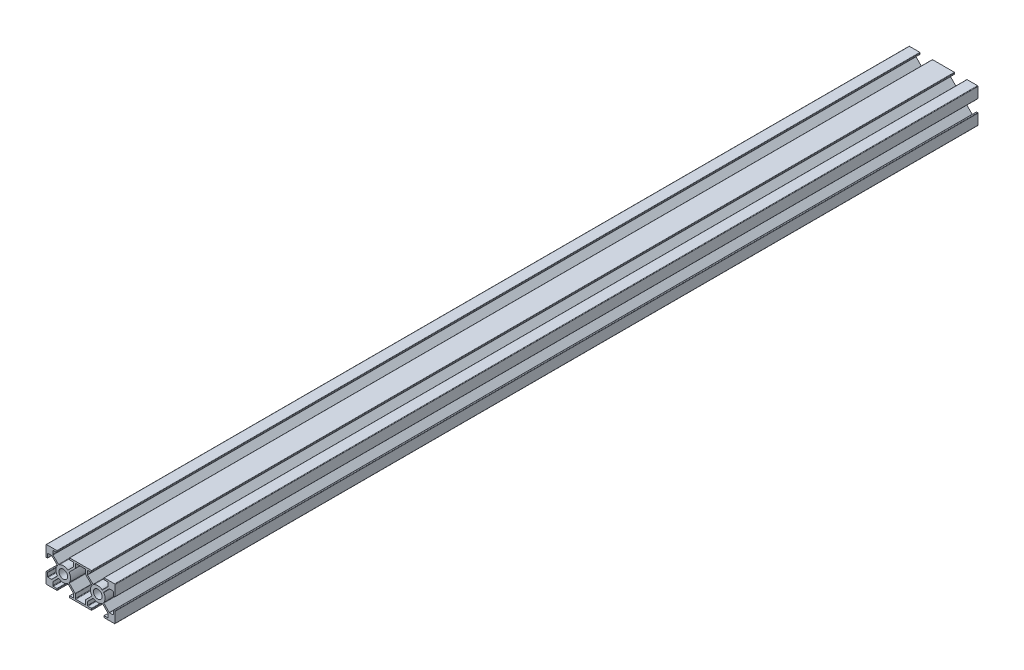
SolidWorks part; units mm, degrees
ref_plane "Front Plane" through (0, 0, 0) normal (0, 0, 1) x (1, 0, 0)
ref_plane "Top Plane" through (0, 0, 0) normal (0, 1, 0) x (1, 0, 0)
ref_plane "Right Plane" through (0, 0, 0) normal (1, 0, 0) x (0, 0, -1)
sketch "Sketch1" plane through (0, 0, 0) normal (0, 0, 1) x (1, 0, 0)
  point P27 (10, 0)
  point P31 (0, -6.2929)
  point P38 (0, 0)
  point P39 (0, 0)
  point P40 (0, 0)
  point P44 (0, 0)
  point P46 (0, 0)
  point P51 (0, 0)
  point P115 (-12.6308, -3.3379)
  point P122 (-16.7071, -6)
  point P134 (-16, 6.7071)
  point P143 (-6.6621, -2.6308)
  point P146 (-7.3692, -3.3379)
  point P167 (3, 6.2929)
  point P173 (-3, 6.2929)
  point P196 (6.6621, 2.6308)
  point P243 (-6.5, 10)
  point P246 (-13.5, 10)
  point P249 (-13.5, 9)
  point P254 (6.5, 10)
  point P259 (13.5, 10)
  point P262 (13.5, 9)
  point P265 (20, 3.5)
  point P268 (19, 3.5)
  point P271 (20, -3.5)
  point P274 (19, -3.5)
  point P277 (13.5, -10)
  point P280 (13.5, -9)
  point P283 (6.5, -10)
  point P286 (6.5, -9)
  point P289 (-6.5, -10)
  point P292 (-6.5, -9)
  point P295 (-13.5, -9)
  point P298 (-13.5, -10)
  point P301 (-19, -3.5)
  point P304 (-20, -3.5)
  point P307 (-19, 3.5)
  point P310 (-20, 3.5)
  line B0 (0, 10) -> (0, -10) construction
  line B1 (-20, -10) -> (20, -10) construction
  line B2 (-20, -10) -> (-20, 10) construction
  line B3 (-20, 10) -> (20, 10) construction
  line B4 (20, -10) -> (20, 10) construction
  line B5 (-20, -10) -> (20, 10) construction
  line B6 (-20, 10) -> (20, -10) construction
  line B7 (-19, -6) -> (-19, 6) construction
  line B8 (19, -6) -> (19, 6) construction
  line B9 (-16, -9) -> (-4, -9) construction
  line B10 (-20, 10) -> (0, -10) construction
  line B11 (0, 10) -> (-20, -10) construction
  line B12 (0, 10) -> (20, -10) construction
  line B13 (20, 10) -> (0, -10) construction
  line B14 (-16.6262, 5.9191) -> (-13.5066, 2.7995)
  line B15 (-15.9191, 6.6262) -> (-12.7995, 3.5066)
  line B16 (3.0809, 6.212) -> (6.4934, 2.7995)
  line B17 (4.0809, 6.6262) -> (7.2005, 3.5066)
  line B18 (15.9191, 6.6262) -> (12.7995, 3.5066)
  line B19 (16.6262, 5.9191) -> (13.5066, 2.7995)
  line B20 (-3.0809, 6.212) -> (-6.6621, 2.6308)
  line B21 (-6.3, -10) -> (6.3, -10)
  line B22 (-7.2005, -3.5066) -> (-4.0809, -6.6262)
  line B23 (-6.4934, -2.7995) -> (-3.0809, -6.212)
  line B24 (-12.7995, -3.5066) -> (-15.9191, -6.6262)
  line B25 (-13.5066, -2.7995) -> (-16.6262, -5.9191)
  line B26 (6.4934, -2.7995) -> (3.0809, -6.212)
  line B27 (7.2005, -3.5066) -> (4.0809, -6.6262)
  line B28 (12.7995, -3.5066) -> (15.9191, -6.6262)
  line B29 (13.5066, -2.7995) -> (16.6262, -5.9191)
  line B30 (-6.3, 10) -> (6.3, 10)
  line B31 (-6.5, 9.8) -> (-6.5, 9.2)
  line B32 (-6.3, 9) -> (-4.2761, 9)
  line B33 (6.5, 9.2) -> (6.5, 9.8)
  line B34 (-6.5, -9.8) -> (-6.5, -9.2)
  line B35 (-6.3, -9) -> (-4.2761, -9)
  line B36 (6.5, -9.2) -> (6.5, -9.8)
  line B37 (-13.7, -10) -> (-19.7239, -10)
  line B38 (-20, -9.7239) -> (-20, -3.7)
  line B39 (-19.8, -3.5) -> (-19.2, -3.5)
  line B40 (-19, -3.7) -> (-19, -5.7239)
  line B41 (-15.7239, -9) -> (-13.7, -9)
  line B42 (-13.5, -9.2) -> (-13.5, -9.8)
  line B43 (13.5, -9.8) -> (13.5, -9.2)
  line B44 (13.7, -9) -> (15.7239, -9)
  line B45 (19, -5.7239) -> (19, -3.7)
  line B46 (19.2, -3.5) -> (19.8, -3.5)
  line B47 (20, -3.7) -> (20, -9.7239)
  line B48 (19.7239, -10) -> (13.7, -10)
  line B49 (20, 3.7) -> (20, 9.7239)
  line B50 (19.7239, 10) -> (13.7, 10)
  line B51 (13.5, 9.8) -> (13.5, 9.2)
  line B52 (13.7, 9) -> (15.7239, 9)
  line B53 (19, 5.7239) -> (19, 3.7)
  line B54 (19.2, 3.5) -> (19.8, 3.5)
  line B55 (-13.7, 10) -> (-19.7239, 10)
  line B56 (-20, 9.7239) -> (-20, 3.7)
  line B57 (-19.8, 3.5) -> (-19.2, 3.5)
  line B58 (-19, 3.7) -> (-19, 5.7239)
  line B59 (-13.5, 9.2) -> (-13.5, 9.8)
  line B60 (-3, -6.2929) -> (3, -6.2929) construction
  line B61 (-4, -6.7071) -> (-4, 6.7071) construction
  line B62 (-3, -6.4073) -> (-3, -8.7239)
  line B63 (-4, -6.8215) -> (-4, -8.7239)
  line B64 (3, -6.4073) -> (3, -8.7239)
  line B65 (4, -6.8215) -> (4, -8.7239)
  line B66 (-2.7239, 9) -> (2.7239, 9)
  line B67 (-3, -6.2929) -> (-3, 9) construction
  line B68 (3, -6.2929) -> (3, 9) construction
  line B69 (4, -6.7071) -> (4, 6.7071) construction
  line B70 (-4, 6.7071) -> (-4, 9) construction
  line B71 (3, 6.4073) -> (3, 8.7239)
  line B72 (4, 6.8215) -> (4, 8.7239)
  line B73 (-3, 6.4073) -> (-3, 8.7239)
  line B74 (-4, 6.8215) -> (-4, 8.7239)
  line B75 (-4.0809, 6.6262) -> (-7.3692, 3.3379)
  line B76 (-3, 9) -> (3, 9) construction
  line B77 (4, 6.7071) -> (4, 9) construction
  line B78 (-16, 8.7239) -> (-16, 6.8215)
  line B79 (-16.8215, 6) -> (-18.7239, 6)
  line B80 (-18.7239, -6) -> (-16.8215, -6)
  line B81 (-16, -6.8215) -> (-16, -8.7239)
  line B82 (18.7239, -6) -> (16.8215, -6)
  line B83 (16, -6.8215) -> (16, -8.7239)
  line B84 (16, 8.7239) -> (16, 6.8215)
  line B85 (16.8215, 6) -> (18.7239, 6)
  line B86 (-16, 9) -> (-4, 9) construction
  line B87 (-15.7239, 9) -> (-13.7, 9)
  line B88 (4.2761, 9) -> (6.3, 9)
  line B89 (4, 9) -> (16, 9) construction
  line B90 (-3, -9) -> (3, -9) construction
  line B91 (-2.7239, -9) -> (2.7239, -9)
  line B92 (4, -9) -> (16, -9) construction
  line B93 (4.2761, -9) -> (6.3, -9)
  circle B94 centre (-10, 0) radius 2.5
  arc B95 (-13.476, 2.4454) -> (-13.476, -2.4454) centre (-10, 0) ccw
  circle B96 centre (10, 0) radius 2.5
  arc B97 (12.4454, 3.476) -> (7.5546, 3.476) centre (10, 0) ccw
  arc B98 (-7.3692, 3.3379) -> (-12.4454, 3.476) centre (-10, 0) ccw
  arc B99 (-12.4454, -3.476) -> (-7.5546, -3.476) centre (-10, 0) ccw
  arc B100 (-6.524, -2.4454) -> (-6.6621, 2.6308) centre (-10, 0) ccw
  arc B101 (6.524, 2.4454) -> (6.524, -2.4454) centre (10, 0) ccw
  arc B102 (7.5546, -3.476) -> (12.4454, -3.476) centre (10, 0) ccw
  arc B103 (13.476, -2.4454) -> (13.476, 2.4454) centre (10, 0) ccw
  arc B104 (-18.7239, -6) -> (-19, -5.7239) centre (-18.7239, -5.7239) cw
  arc B105 (-16, -8.7239) -> (-15.7239, -9) centre (-15.7239, -8.7239) ccw
  arc B106 (-12.7995, -3.5066) -> (-12.4454, -3.476) centre (-12.6042, -3.7019) cw
  arc B107 (-13.5066, -2.7995) -> (-13.476, -2.4454) centre (-13.7019, -2.6042) ccw
  arc B108 (-16, -6.8215) -> (-15.9191, -6.6262) centre (-15.7239, -6.8215) cw
  arc B109 (-16.8215, -6) -> (-16.6262, -5.9191) centre (-16.8215, -5.7239) ccw
  arc B110 (-12.7995, 3.5066) -> (-12.4454, 3.476) centre (-12.6042, 3.7019) ccw
  arc B111 (-13.5066, 2.7995) -> (-13.476, 2.4454) centre (-13.7019, 2.6042) cw
  arc B112 (-18.7239, 6) -> (-19, 5.7239) centre (-18.7239, 5.7239) ccw
  arc B113 (-16.6262, 5.9191) -> (-16.8215, 6) centre (-16.8215, 5.7239) ccw
  arc B114 (-15.9191, 6.6262) -> (-16, 6.8215) centre (-15.7239, 6.8215) cw
  arc B115 (-16, 8.7239) -> (-15.7239, 9) centre (-15.7239, 8.7239) cw
  arc B116 (-4, 8.7239) -> (-4.2761, 9) centre (-4.2761, 8.7239) ccw
  arc B117 (-6.4934, -2.7995) -> (-6.524, -2.4454) centre (-6.2981, -2.6042) cw
  arc B118 (-7.2005, -3.5066) -> (-7.5546, -3.476) centre (-7.3958, -3.7019) ccw
  arc B119 (-3.0809, -6.212) -> (-3, -6.4073) centre (-3.2761, -6.4073) cw
  arc B120 (-4, -6.8215) -> (-4.0809, -6.6262) centre (-4.2761, -6.8215) ccw
  arc B121 (-4.2761, -9) -> (-4, -8.7239) centre (-4.2761, -8.7239) ccw
  arc B122 (-3, -8.7239) -> (-2.7239, -9) centre (-2.7239, -8.7239) ccw
  arc B123 (3, -8.7239) -> (2.7239, -9) centre (2.7239, -8.7239) cw
  arc B124 (4.0809, 6.6262) -> (4, 6.8215) centre (4.2761, 6.8215) cw
  arc B125 (3.0809, 6.212) -> (3, 6.4073) centre (3.2761, 6.4073) cw
  arc B126 (-4.0809, 6.6262) -> (-4, 6.8215) centre (-4.2761, 6.8215) ccw
  arc B127 (-3.0809, 6.212) -> (-3, 6.4073) centre (-3.2761, 6.4073) ccw
  arc B128 (-2.7239, 9) -> (-3, 8.7239) centre (-2.7239, 8.7239) ccw
  arc B129 (2.7239, 9) -> (3, 8.7239) centre (2.7239, 8.7239) cw
  arc B130 (4, 8.7239) -> (4.2761, 9) centre (4.2761, 8.7239) cw
  arc B131 (3, -6.4073) -> (3.0809, -6.212) centre (3.2761, -6.4073) cw
  arc B132 (4.0809, -6.6262) -> (4, -6.8215) centre (4.2761, -6.8215) ccw
  arc B133 (4.2761, -9) -> (4, -8.7239) centre (4.2761, -8.7239) cw
  arc B134 (6.524, -2.4454) -> (6.4934, -2.7995) centre (6.2981, -2.6042) cw
  arc B135 (6.4934, 2.7995) -> (6.524, 2.4454) centre (6.2981, 2.6042) cw
  arc B136 (7.2005, 3.5066) -> (7.5546, 3.476) centre (7.3958, 3.7019) ccw
  arc B137 (12.4454, 3.476) -> (12.7995, 3.5066) centre (12.6042, 3.7019) ccw
  arc B138 (13.476, 2.4454) -> (13.5066, 2.7995) centre (13.7019, 2.6042) cw
  arc B139 (13.476, -2.4454) -> (13.5066, -2.7995) centre (13.7019, -2.6042) ccw
  arc B140 (12.4454, -3.476) -> (12.7995, -3.5066) centre (12.6042, -3.7019) cw
  arc B141 (7.5546, -3.476) -> (7.2005, -3.5066) centre (7.3958, -3.7019) ccw
  arc B142 (16.8215, -6) -> (16.6262, -5.9191) centre (16.8215, -5.7239) cw
  arc B143 (16, -6.8215) -> (15.9191, -6.6262) centre (15.7239, -6.8215) ccw
  arc B144 (16, -8.7239) -> (15.7239, -9) centre (15.7239, -8.7239) cw
  arc B145 (18.7239, -6) -> (19, -5.7239) centre (18.7239, -5.7239) ccw
  arc B146 (15.9191, 6.6262) -> (16, 6.8215) centre (15.7239, 6.8215) ccw
  arc B147 (16.6262, 5.9191) -> (16.8215, 6) centre (16.8215, 5.7239) cw
  arc B148 (18.7239, 6) -> (19, 5.7239) centre (18.7239, 5.7239) cw
  arc B149 (16, 8.7239) -> (15.7239, 9) centre (15.7239, 8.7239) ccw
  arc B150 (19.7239, 10) -> (20, 9.7239) centre (19.7239, 9.7239) cw
  arc B151 (19.7239, -10) -> (20, -9.7239) centre (19.7239, -9.7239) ccw
  arc B152 (-20, -9.7239) -> (-19.7239, -10) centre (-19.7239, -9.7239) ccw
  arc B153 (-20, 9.7239) -> (-19.7239, 10) centre (-19.7239, 9.7239) cw
  arc B154 (-6.3, 10) -> (-6.5, 9.8) centre (-6.3, 9.8) ccw
  arc B155 (-13.5, 9.8) -> (-13.7, 10) centre (-13.7, 9.8) ccw
  arc B156 (-13.7, 9) -> (-13.5, 9.2) centre (-13.7, 9.2) ccw
  arc B157 (-6.5, 9.2) -> (-6.3, 9) centre (-6.3, 9.2) ccw
  arc B158 (6.3, 10) -> (6.5, 9.8) centre (6.3, 9.8) cw
  arc B159 (6.3, 9) -> (6.5, 9.2) centre (6.3, 9.2) ccw
  arc B160 (13.7, 10) -> (13.5, 9.8) centre (13.7, 9.8) ccw
  arc B161 (13.5, 9.2) -> (13.7, 9) centre (13.7, 9.2) ccw
  arc B162 (20, 3.7) -> (19.8, 3.5) centre (19.8, 3.7) cw
  arc B163 (19, 3.7) -> (19.2, 3.5) centre (19.2, 3.7) ccw
  arc B164 (19.8, -3.5) -> (20, -3.7) centre (19.8, -3.7) cw
  arc B165 (19, -3.7) -> (19.2, -3.5) centre (19.2, -3.7) cw
  arc B166 (13.5, -9.8) -> (13.7, -10) centre (13.7, -9.8) ccw
  arc B167 (13.5, -9.2) -> (13.7, -9) centre (13.7, -9.2) cw
  arc B168 (6.3, -10) -> (6.5, -9.8) centre (6.3, -9.8) ccw
  arc B169 (6.3, -9) -> (6.5, -9.2) centre (6.3, -9.2) cw
  arc B170 (-6.5, -9.8) -> (-6.3, -10) centre (-6.3, -9.8) ccw
  arc B171 (-6.5, -9.2) -> (-6.3, -9) centre (-6.3, -9.2) cw
  arc B172 (-13.7, -9) -> (-13.5, -9.2) centre (-13.7, -9.2) cw
  arc B173 (-13.5, -9.8) -> (-13.7, -10) centre (-13.7, -9.8) cw
  arc B174 (-19.2, -3.5) -> (-19, -3.7) centre (-19.2, -3.7) cw
  arc B175 (-19.8, -3.5) -> (-20, -3.7) centre (-19.8, -3.7) ccw
  arc B176 (-19.2, 3.5) -> (-19, 3.7) centre (-19.2, 3.7) ccw
  arc B177 (-20, 3.7) -> (-19.8, 3.5) centre (-19.8, 3.7) ccw
  dimension "D19" = 13
  dimension "D20" = 13
  dimension "D32" = 1
  dimension "D33" = 2.5
  dimension "D35" = 2.5
  dimension "D36" = 2.5
  dimension "D37" = 2.5
  dimension "D38" = 2.5
  dimension "D39" = 2.5
  dimension "D40" = 2.2929
  dimension "D41" = 1
sketch_block_instance "Block1-1"
sketch_block "Block1" parameters "D11"=2.5, "D12"=4.25, "D13"=2.5, "D14"=4.25, "D28"=0.2761, "D29"=0.2, "D1"=40, "D2"=20, "D3"=6.5, "D4"=6.5, "D5"=6.5, "D6"=6.5, "D7"=6.5, "D8"=6.5, "D9"=6.5, "D10"=6.5, "D15"=1, "D16"=6, "D17"=1, "D18"=1, "D19"=1, "D20"=1, "D21"=1, "D22"=0.5, "D23"=1, "D24"=0.5, "D25"=1, "D26"=0.5, "D27"=0.5
extrude "Boss-Extrude1" add sketch "Sketch1" along normal blind 500
